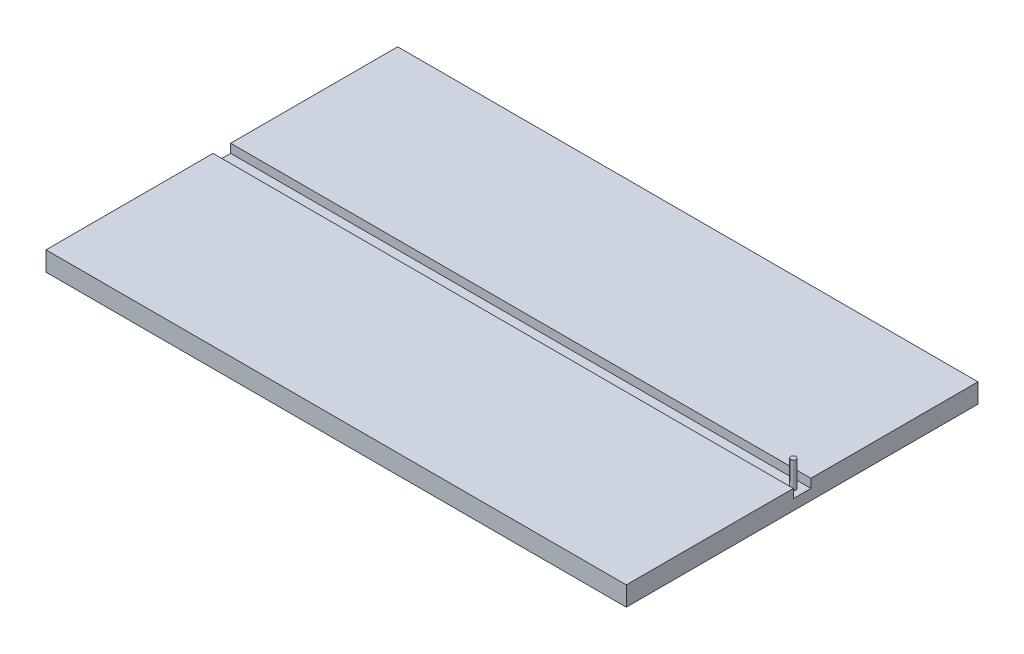
SolidWorks part; units mm, degrees
material "PBT General Purpose"
ref_plane "Front Plane" through (0, 0, 0) normal (0, 0, 1) x (1, 0, 0)
ref_plane "Top Plane" through (0, 0, 0) normal (0, 1, 0) x (1, 0, 0)
ref_plane "Right Plane" through (0, 0, 0) normal (1, 0, 0) x (0, 0, -1)
sketch "Sketch1" plane through (0, 0, 0) normal (0, 1, 0) x (1, 0, 0)
  line L1 (0, 0) -> (330, 0)
  line L2 (0, 0) -> (0, 200)
  line L3 (0, 200) -> (330, 200)
  line L4 (330, 0) -> (330, 200)
  dimension "D1" = 330
extrude "Boss-Extrude1" add sketch "Sketch1" along normal blind 6
sketch "Sketch2" plane through (0, 6, 0) normal (0, 1, 0) x (1, 0, 0)
  line L0 (330, 0) -> (330, 200) construction
  line L1 (0, 0) -> (330, 0)
  line L2 (0, 0) -> (0, 95)
  line L3 (0, 95) -> (330, 95)
  line L4 (330, 0) -> (330, 95)
  line L6 (0, 200) -> (330, 200)
  line L7 (0, 200) -> (0, 105)
  line L8 (0, 105) -> (330, 105)
  line L9 (330, 200) -> (330, 105)
extrude "Boss-Extrude2" add sketch "Sketch2" along normal blind 5
sketch "Sketch3" plane through (0, 6, 0) normal (0, 1, 0) x (1, 0, 0)
  line L0 (0, 105) -> (330, 105) construction
  line L1 (330, 95) -> (330, 105) construction
  circle A0 centre (325, 100) radius 1.5
  dimension "D1" = 5
  dimension "D2" = 5
extrude "Boss-Extrude3" add sketch "Sketch3" along normal blind 15
